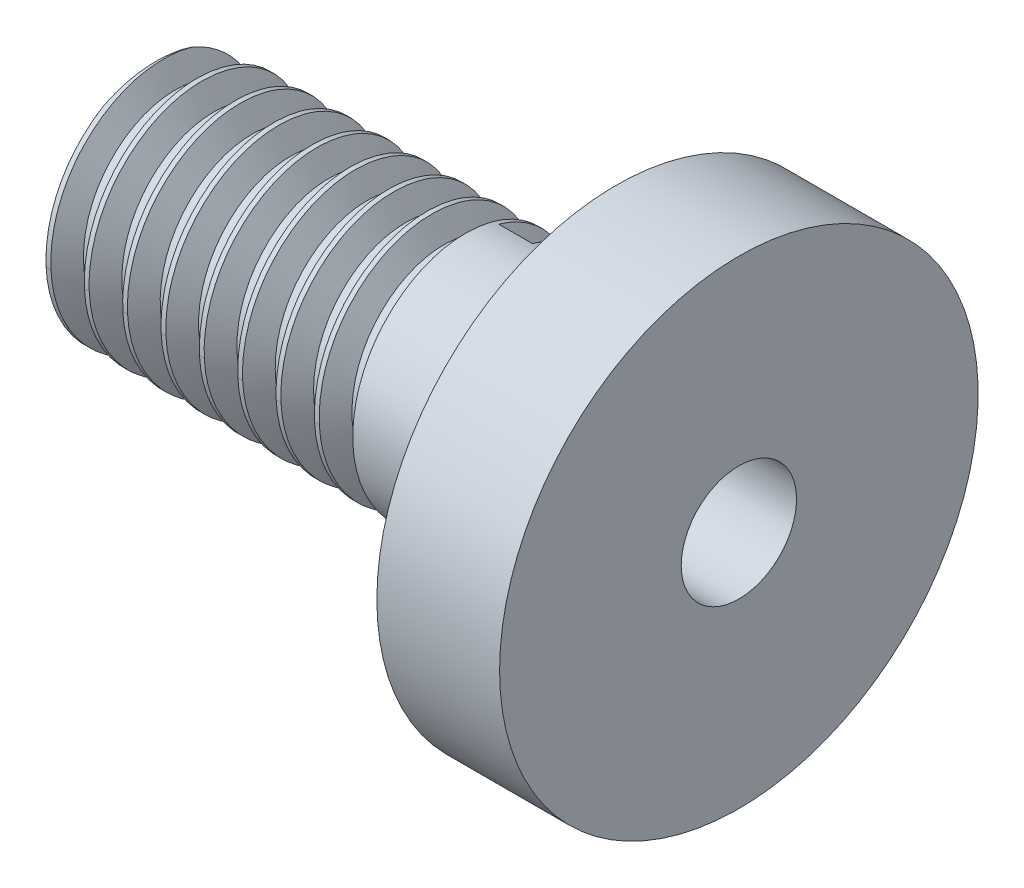
SolidWorks part; units mm, degrees
ref_plane "Front Plane" through (0, 0, 0) normal (0, 0, 1) x (1, 0, 0)
ref_plane "Top Plane" through (0, 0, 0) normal (0, 1, 0) x (1, 0, 0)
ref_plane "Right Plane" through (0, 0, 0) normal (1, 0, 0) x (0, 0, -1)
sketch "Sketch1" plane through (0, 0, 0) normal (0, 1, 0) x (1, 0, 0)
  line L0 (-9.525, 1.1938) -> (2.54, 1.1938)
  line L1 (2.54, 1.1938) -> (2.54, 4.953)
  line L2 (2.54, 4.953) -> (0, 4.953)
  line L3 (0, 4.953) -> (0, 2.413)
  line L4 (0, 2.413) -> (-9.525, 2.413)
  line L5 (-9.525, 2.413) -> (-9.525, 1.1938)
  line L6 (0, 0) -> (4.0765, 0) construction
  dimension "D1" = 4.826
  dimension "D2" = 2.3876
  dimension "D3" = 9.525
  dimension "D4" = 2.54
  dimension "D5" = 2.54
revolve "Revolve1" add sketch "Sketch1" angle 360 about L6
thread "Thread1" pitch 0.7937 start angle 0, offset 2.54, length 6.35, pitch 0.7937, diameter 4.826
ref_plane "Plane1" through (-12.065, 0, -2.413) normal (0, -1, 0) x (0, 0, -1)
sketch "Thread Profile1" plane through (-12.065, 0, -2.413) normal (0, -1, 0) x (0, 0, -1)
  line L0 (0, 0) -> (0, 0.7937) construction
  line L11 (0, 0) -> (0, 0.6945)
  line L12 (0, 0.6945) -> (-0.4296, 0.4465)
  line L13 (-0.4296, 0.4465) -> (-0.4296, 0.248)
  line L15 (-0.4296, 0.248) -> (0, 0)
  line L17 (-0.4296, 0.3473) -> (0, 0.3473) construction
  point P2 (0, 0)
  dimension "Pitch" = 0.7937
  dimension "Profile_Angle" = 60
  dimension "Profile_Land" = 0.1984
  dimension "Profile_Height" = 0.4296
